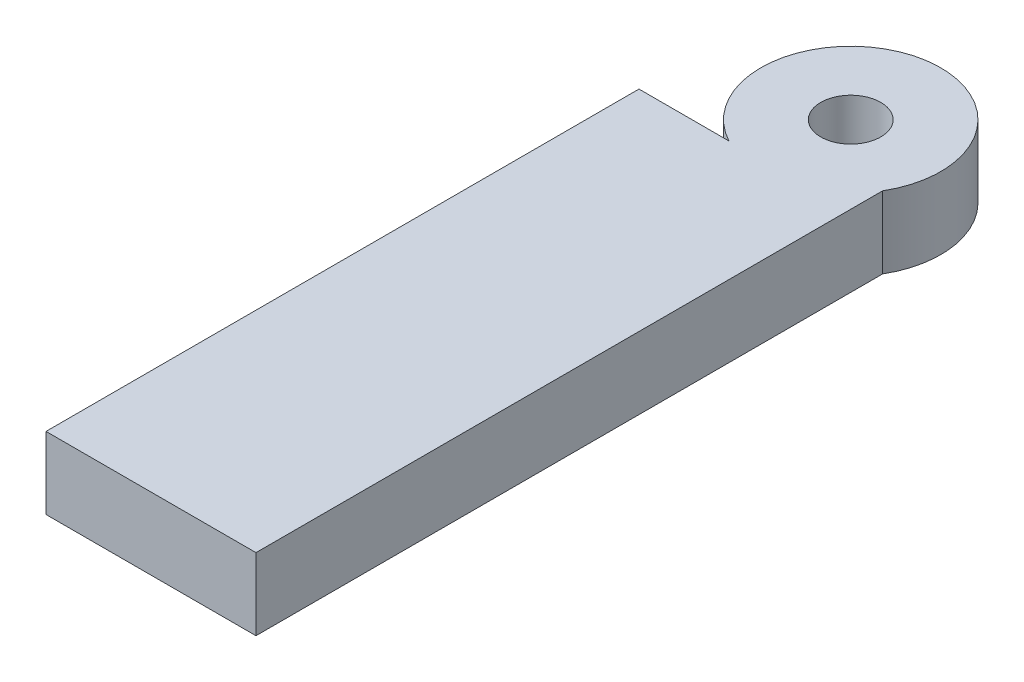
SolidWorks part; units mm, degrees
ref_plane "Front Plane" through (0, 0, 0) normal (0, 0, 1) x (1, 0, 0)
ref_plane "Top Plane" through (0, 0, 0) normal (0, 1, 0) x (1, 0, 0)
ref_plane "Right Plane" through (0, 0, 0) normal (1, 0, 0) x (0, 0, -1)
sketch "Sketch1" plane through (0, 0, 0) normal (0, 1, 0) x (1, 0, 0)
  line L0 (0, 9.525) -> (-4.4901, 5.0349)
  line L1 (0, 9.525) -> (0, 0) construction
  line L2 (-4.4901, -71.1651) -> (8.2099, -71.1651)
  line L3 (-4.4901, 5.0349) -> (-4.4901, -71.1651)
  line L4 (8.2099, -71.1651) -> (8.2099, -4.8295)
  circle A0 centre (0, 0) radius 3.175
  circle A1 centre (0, 0) radius 9.525
  dimension "D1" = 6.35
  dimension "D2" = 19.05
  dimension "D3" = 45
  dimension "D4" = 6.35
  dimension "D5" = 76.2
  dimension "D6" = 12.7
extrude "Boss-Extrude1" add sketch "Sketch1" along normal blind 7.62 region at (6.568, 0, -6.568) region at (-6.1109, 0, -0.9585) region at (1.9114, 0, 39.8268)
sketch "Sketch2" plane through (-4.4901, 0, 0) normal (-1, 0, 0) x (0, 0, 1)
  line L1 (8.4003, 7.62) -> (71.1651, 7.62) construction
  line L2 (8.4003, 7.62) -> (8.4003, 0) construction
  circle A0 centre (14.7503, 3.81) radius 2.54
  circle A1 centre (52.8503, 3.81) radius 2.54
  dimension "D1" = 5.08
  dimension "D2" = 5.08
  dimension "D3" = 6.35
  dimension "D4" = 3.81
  dimension "D5" = 38.1
extrude "Cut-Extrude1" cut sketch "Sketch2" against normal blind 6.35
sketch "Sketch3" plane through (-4.4901, 0, 0) normal (-1, 0, 0) x (0, 0, 1)
  line L4 (8.4003, 0) -> (71.1651, 0)
  line L5 (71.1651, 0) -> (71.1651, 7.62)
  line L6 (71.1651, 7.62) -> (8.4003, 7.62)
  line L7 (8.4003, 7.62) -> (8.4003, 0)
  line L8 (8.4003, 0) -> (71.1651, 0)
  line L9 (71.1651, 0) -> (71.1651, 7.62)
  line L10 (71.1651, 7.62) -> (8.4003, 7.62)
  line L12 (8.4003, 7.62) -> (8.4003, 0)
  circle A0 centre (52.8503, 3.81) radius 2.54 construction
  circle A1 centre (14.7503, 3.81) radius 2.54 construction
  circle A2 centre (52.8503, 3.81) radius 2.54
  circle A3 centre (14.7503, 3.81) radius 2.54
  dimension "D1" = 0
extrude "Boss-Extrude2" add sketch "Sketch3" along normal blind 9.525
sketch "Sketch4" [suppressed] plane through (-17.9605, 0, 0) normal (-1, 0, 0) x (0, 0, 1)
  line L4 (8.4355, 0) -> (59.2355, 0)
  line L5 (59.2355, 0) -> (59.2355, 7.62)
  line L6 (59.2355, 7.62) -> (8.4355, 7.62)
  line L7 (8.4355, 7.62) -> (8.4355, 0)
  line L8 (8.4355, 0) -> (59.2355, 0)
  line L9 (59.2355, 0) -> (59.2355, 7.62)
  line L10 (59.2355, 7.62) -> (8.4355, 7.62)
  line L11 (8.4355, 7.62) -> (8.4355, 0)
  circle A0 centre (52.8855, 3.81) radius 1.27 construction
  circle A1 centre (14.7855, 3.81) radius 1.27 construction
  circle A2 centre (52.8855, 3.81) radius 1.27
  circle A3 centre (14.7855, 3.81) radius 1.27
  dimension "D1" = 0
extrude "Boss-Extrude3" [suppressed] add sketch "Sketch4" along normal blind 4.7625
